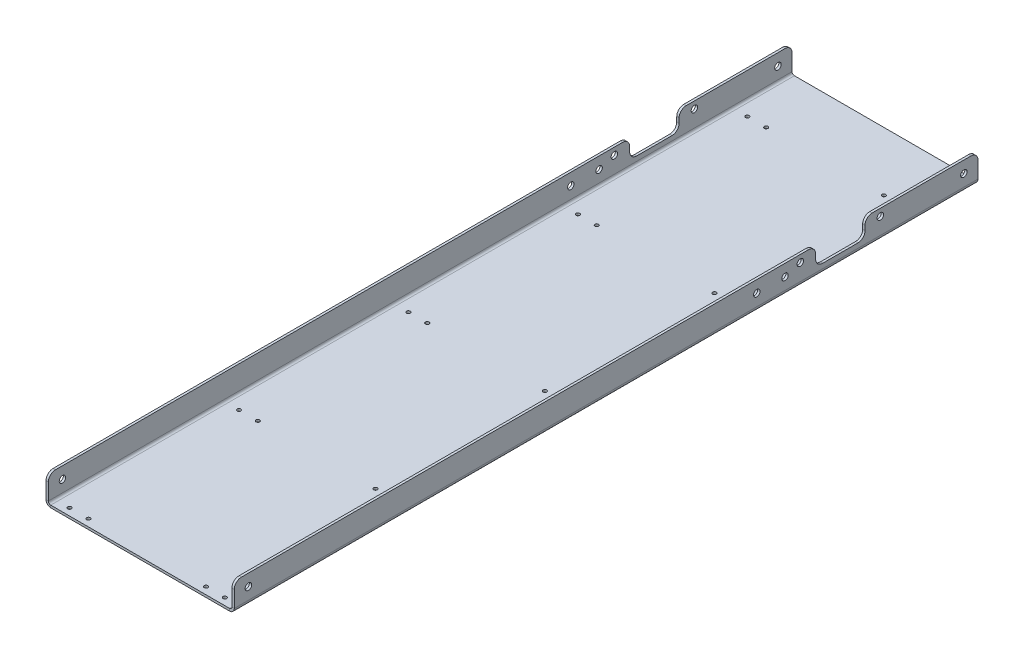
SolidWorks part; units mm, degrees
note: The reader was unsure of these and kept them because the rebuilt part matched: thickness of "Base-Flange1", "Edge-Flange1", "Sheet-Metal1", "Sheet-Metal2", "Sheet-Metal5", "Sheet-Metal6", "Sheet-Metal9"; flange length of "Edge-Flange1".
material "5052-H32"
ref_plane "Front Plane" through (0, 0, 0) normal (0, 0, 1) x (1, 0, 0)
ref_plane "Top Plane" through (0, 0, 0) normal (0, 1, 0) x (1, 0, 0)
ref_plane "Right Plane" through (0, 0, 0) normal (1, 0, 0) x (0, 0, -1)
sketch "Sketch1" plane through (0, 0, 0) normal (0, 1, 0) x (1, 0, 0)
  line L1 (-127, 0) -> (127, 0)
  line L2 (-127, 0) -> (-127, -1003.3)
  line L3 (-127, -1003.3) -> (127, -1003.3)
  line L4 (127, 0) -> (127, -1003.3)
  point P4 (0, 0)
  dimension "D1" = 254
  dimension "D2" = 1003.3
base flange "Base-Flange1" sketch "Sketch1" thickness 3.175 reverse thickness direction no parameters "D1"=3.175
edge flange "Edge-Flange1" sketch "Sketch10" flange profiles "Sketch10", "Sketch11" flange angle 90 flange length 38.1 flange position material inside bend radius 3.175 thickness 3.175 relief rectangular parameters "D1"=3.9688, "D6"=10, "D8"=1
sketch "Sketch10" plane through (-127, 0, 0) normal (-1, 0, 0) x (0, 0, 1)
  line L2 (0, 0) -> (0, 34.925)
  line L3 (0, 34.925) -> (1003.3, 34.925)
  line L4 (1003.3, 34.925) -> (1003.3, 0)
  line L7 (0, 0) -> (1003.3, 0) construction
  line L8 (0, 0) -> (1003.3, 0)
sketch "Sketch11" plane through (127, 0, 0) normal (1, 0, 0) x (0, 0, -1)
  line L0 (-1003.3, 0) -> (0, 0) construction
  line L1 (-1003.3, 0) -> (0, 0)
  line L2 (-1003.3, 0) -> (-1003.3, 34.925)
  line L3 (-1003.3, 34.925) -> (0, 34.925)
  line L4 (0, 34.925) -> (0, 0)
bend "EdgeBend1" bend radius 3.175 bend angle 90 parameters "D5"=1
bend "EdgeBend2" bend radius 3.175 bend angle 90 parameters "D5"=2
sketch "Sketch30" plane through (-127, 0, 0) normal (-1, 0, 0) x (0, 0, 1)
  line L0 (1003.3, 34.925) -> (0, 34.925) construction
  line L1 (152.4, 34.925) -> (219.075, 34.925)
  line L2 (152.4, 34.925) -> (152.4, 9.525)
  line L3 (152.4, 9.525) -> (219.075, 9.525)
  line L4 (219.075, 34.925) -> (219.075, 9.525)
  line L5 (0, 34.925) -> (0, 3.175) construction
  line L6 (1003.3, 0) -> (0, 0) construction
  point P8 (152.4, 22.225)
  point P11 (185.7375, 9.525)
  dimension "D1" = 152.4
  dimension "D2" = 66.675
  dimension "D3" = 9.525
extrude "Cut-Extrude4" cut sketch "Sketch30" against normal through all normal cut yes
sketch "Sketch15" plane through (-127, 0, 0) normal (-1, 0, 0) x (0, 0, 1)
  line L0 (279.4, 34.925) -> (279.4, -3.175) construction
  line L1 (1003.3, 34.925) -> (219.075, 34.925) construction
  line L2 (1003.3, -3.175) -> (0, -3.175) construction
  line L3 (0, 34.925) -> (0, 3.175) construction
  line L4 (0, 19.05) -> (1003.3, 19.05) construction
  line L5 (1003.3, 3.175) -> (1003.3, 34.925) construction
  line L6 (131.7625, 25.4) -> (239.7125, 25.4) construction
  point P12 (260.35, 19.05)
  point P13 (19.05, 19.05)
  point P14 (298.45, 19.05)
  point P15 (984.25, 19.05)
  point P16 (603.25, 19.05)
  dimension "D1" = 279.4
  dimension "D2" = 22.225
  dimension "D3" = 6.35
  dimension "D4" = 19.05
  dimension "D5" = 19.05
  dimension "D6" = 112.7125
  dimension "D7" = 19.05
  dimension "D8" = 19.05
  dimension "D9" = 381
  dimension "D10" = 107.95
hole_wizard "Hole for 1/4 Self-clinching Nuts (S,SS,CLS,CLSS)1" positions "Sketch16" profile "Sketch17" hole size "1/4-20" standard "PEM® Inch" end condition through all
sketch "Sketch16" plane through (-127, 0, 0) normal (-1, 0, 0) x (0, 0, 1)
  point P0 (19.05, 19.05)
  point P6 (260.35, 19.05)
  point P9 (298.45, 19.05)
  point P15 (984.25, 19.05)
  point P18 (239.7125, 25.4)
  point P20 (131.7625, 25.4)
sketch "Sketch17" plane through (-127, 19.05, 19.05) normal (0, 1, 0) x (0, 0, 1)
  line L0 (0, 0) -> (0, 254)
  line L1 (0, 254) -> (4.3688, 254)
  line L2 (4.3688, 254) -> (4.3688, 0)
  line L5 (4.3688, 0) -> (0, 0)
  line L11 (0, -6.35) -> (0, 107.95) construction
  dimension "Thru Hole Dia." = 8.7376
  dimension "Thru Hole Depth" = 254
sketch "Sketch19" plane through (0, 0, 0) normal (0, 1, 0) x (1, 0, 0)
  line L0 (120.65, 0) -> (-120.65, 0) construction
  line L1 (-104.775, 0) -> (104.775, 0) construction
  line L2 (-104.775, 0) -> (-104.775, -1003.3) construction
  line L3 (-104.775, -1003.3) -> (104.775, -1003.3) construction
  line L4 (104.775, 0) -> (104.775, -1003.3) construction
  line L5 (-120.65, -1003.3) -> (120.65, -1003.3) construction
  line L8 (-104.775, -536.575) -> (104.775, -536.575) construction
  line L9 (-79.375, 0) -> (-79.375, -1003.3) construction
  line L10 (-104.775, -765.175) -> (104.775, -765.175) construction
  line L13 (79.375, 0) -> (79.375, -1003.3) construction
  line L16 (-104.775, -993.775) -> (104.775, -993.775) construction
  line L17 (-104.775, -79.375) -> (104.775, -79.375) construction
  line L19 (-104.775, -307.975) -> (104.775, -307.975) construction
  point P8 (0, -993.775)
  point P30 (-79.375, -536.575)
  point P31 (-79.375, -765.175)
  point P32 (79.375, -765.175)
  point P33 (-79.375, -993.775)
  point P34 (79.375, -993.775)
  point P35 (-79.375, -79.375)
  point P36 (79.375, -79.375)
  point P37 (79.375, -536.575)
  point P38 (79.375, -307.975)
  point P39 (-79.375, -307.975)
  dimension "D2" = 104.775
  dimension "D3" = 9.525
  dimension "D4" = 25.4
  dimension "D5" = 228.6
  dimension "D6" = 79.375
  dimension "D11" = 228.6
  dimension "D12" = 228.6
  dimension "D13" = 79.375
hole_wizard "#10 (0.1935) Diameter Hole1" positions "Sketch20" profile "Sketch21" hole size "#10" standard "ANSI Inch" end condition through all
sketch "Sketch20" plane through (0, 0, 0) normal (0, 1, 0) x (1, 0, 0)
  point P87 (104.775, -79.375)
  point P89 (79.375, -79.375)
  point P91 (-79.375, -79.375)
  point P93 (-104.775, -79.375)
  point P95 (-104.775, -307.975)
  point P97 (-79.375, -307.975)
  point P99 (79.375, -307.975)
  point P101 (104.775, -307.975)
  point P103 (104.775, -536.575)
  point P105 (79.375, -536.575)
  point P107 (-79.375, -765.175)
  point P109 (-79.375, -536.575)
  point P111 (-104.775, -536.575)
  point P113 (-104.775, -765.175)
  point P115 (79.375, -765.175)
  point P117 (104.775, -765.175)
  point P119 (104.775, -993.775)
  point P121 (79.375, -993.775)
  point P123 (-79.375, -993.775)
  point P125 (-104.775, -993.775)
sketch "Sketch21" plane through (104.775, 0, 79.375) normal (1, 0, 0) x (0, 0, 1)
  line L0 (0, 0) -> (0, 3.175)
  line L1 (0, 3.175) -> (2.4574, 3.175)
  line L2 (2.4574, 3.175) -> (2.4574, 0)
  line L5 (2.4574, 0) -> (0, 0)
  line L11 (0, -6.35) -> (0, 107.95) construction
  dimension "Thru Hole Dia." = 4.9149
  dimension "Thru Hole Depth" = 3.175
sketch "Sketch25" plane through (0, 0, 0) normal (0, 1, 0) x (1, 0, 0)
  line L0 (-111.125, -174.625) -> (-92.075, -174.625)
  line L1 (-104.775, -152.4) -> (-98.425, -152.4)
  line L2 (-104.775, -152.4) -> (-104.775, -174.625)
  line L3 (-104.775, -174.625) -> (-98.425, -174.625)
  line L4 (-98.425, -152.4) -> (-98.425, -174.625)
  line L5 (-92.075, -174.625) -> (-101.6, -184.15)
  line L6 (-101.6, -184.15) -> (-111.125, -174.625)
  line L7 (-101.6, -184.15) -> (-101.6, -152.4) construction
  line L11 (0, 0) -> (0, -1003.3) construction
  line L12 (-120.65, -1003.3) -> (120.65, -1003.3) construction
  line L13 (-101.6, -184.15) -> (-92.075, -174.625)
  line L14 (-111.125, -174.625) -> (-101.6, -184.15)
  line L15 (-104.775, -152.4) -> (-104.775, -174.625)
  line L16 (-98.425, -152.4) -> (-98.425, -174.625)
  line L17 (101.6, -184.15) -> (101.6, -152.4) construction
  line L18 (101.6, -184.15) -> (111.125, -174.625)
  line L19 (101.6, -184.15) -> (92.075, -174.625)
  line L20 (92.075, -174.625) -> (101.6, -184.15)
  line L21 (111.125, -174.625) -> (92.075, -174.625)
  line L22 (98.425, -152.4) -> (98.425, -174.625)
  line L23 (104.775, -152.4) -> (98.425, -152.4)
  line L24 (104.775, -152.4) -> (104.775, -174.625)
  line L25 (-123.825, 0) -> (-123.825, -1003.3) construction
  line L26 (120.65, 0) -> (-120.65, 0) construction
  point P8 (-101.6, -174.625)
  dimension "D1" = 31.75
  dimension "D2" = 9.525
  dimension "D3" = 6.35
  dimension "D4" = 6.35
  dimension "D5" = 12.7
  dimension "D6" = 152.4
fillet "Fillet5" radius 9.525 12 edges at (-125.4125, 34.925, 1003.3) (125.4125, 34.925, 1003.3) (125.4125, 9.525, 219.075) (125.4125, 34.925, 219.075) (-125.4125, 34.925, 219.075) (-125.4125, 9.525, 219.075) (-125.4125, 9.525, 152.4) (125.4125, 9.525, 152.4) (125.4125, 34.925, 152.4) (-125.4125, 34.925, 152.4) (-125.4125, 34.925, 0) (125.4125, 34.925, 0)
sketch "Bend-Lines1" [suppressed] plane through (0, 0, 0) normal (0, 1, 0) x (1, 0, 0)
sketch "Bounding-Box1" [suppressed] plane through (0, 0, 0) normal (0, 1, 0) x (1, 0, 0)
sheet metal parameters "Sheet-Metal1" thickness 3.175 parameters "D1"=2.9766, "D7"=1.9844
flat pattern "Flat-Pattern1" [suppressed]
sketch "Bend-Lines2" plane through (0, 0, 0) normal (0, 1, 0) x (1, 0, 0)
sketch3d "Bounding-Box2" [suppressed]
  line L0 (127, 0, 0) -> (127, -1003.3, 0) construction
  line L1 (-127, 0, 0) -> (-127, -1003.3, 0) construction
  line L2 (127, 0, 0) -> (-127, 0, 0) construction
  line L3 (127, -1003.3, 0) -> (-127, -1003.3, 0) construction
sheet metal parameters "Sheet-Metal2" thickness 3.175 parameters "D1"=2.9766, "D7"=1.9844
flat pattern "Flat-Pattern1" [suppressed]
sketch "Bend-Lines2" plane through (0, 0, 0) normal (0, 1, 0) x (1, 0, 0)
  line L0 (124.2201, -1003.3) -> (124.2201, 0) construction
  line L1 (-124.2201, 0) -> (-124.2201, -1003.3) construction
  line L2 (124.2201, -1003.3) -> (124.2201, 0) construction
  line L3 (-124.2201, 0) -> (-124.2201, -1003.3) construction
sketch3d "Bounding-Box2" [suppressed]
  line L0 (-159.5402, 0, 0) -> (-159.5402, -1003.3, 0) construction
  line L1 (159.5402, 0, 0) -> (159.5402, -1003.3, 0) construction
  line L2 (-159.5402, 0, 0) -> (159.5402, 0, 0) construction
  line L3 (-159.5402, -1003.3, 0) -> (159.5402, -1003.3, 0) construction
bend of the flat pattern "Flatten-<EdgeBend1>1"
bend of the flat pattern "Flatten-<EdgeBend2>1"
sketch "Sketch15-4" plane through (-124.6152, -3.175, 0) normal (0, -1, 0) x (0, 0, 1)
  line L0 (279.4, 34.925) -> (279.4, -3.175) construction
  line L2 (1003.3, -3.175) -> (0, -3.175) construction
  line L3 (0, 34.925) -> (0, -284.1555) construction
  line L4 (0, 19.05) -> (1003.3, 19.05) construction
  line L5 (1003.3, -284.1555) -> (1003.3, 34.925) construction
  line L6 (252.4125, 34.925) -> (252.4125, 3.9688) construction
  line L7 (119.0625, 34.925) -> (119.0625, 3.9688) construction
  line L9 (119.0625, 3.9688) -> (119.0625, 34.925) construction
  point P12 (260.35, 19.05)
  point P13 (19.05, 19.05)
  point P14 (298.45, 19.05)
  point P15 (984.25, 19.05)
  point P16 (603.25, 19.05)
  point P19 (106.3625, 19.05)
  point P22 (111.125, 19.05)
  dimension "D1" = 279.4
  dimension "D2" = 22.225
  dimension "D3" = 26.9875
  dimension "D4" = 19.05
  dimension "D5" = 19.05
  dimension "D6" = 12.7
  dimension "D7" = 19.05
  dimension "D8" = 19.05
  dimension "D9" = 381
  dimension "D10" = 87.3125
  dimension "D11" = 7.9375
  dimension "D12" = 92.075
sheet metal parameters "Sheet-Metal5" thickness 3.175 parameters "D1"=2.9766, "D7"=1.9844
flat pattern "Flat-Pattern1" [suppressed]
sketch "Bend-Lines2" plane through (0, 0, 0) normal (0, 1, 0) x (1, 0, 0)
  line L0 (124.2201, -1003.3) -> (124.2201, 0) construction
  line L1 (-124.2201, 0) -> (-124.2201, -1003.3) construction
  line L2 (124.2201, -1003.3) -> (124.2201, 0) construction
  line L3 (-124.2201, 0) -> (-124.2201, -1003.3) construction
sketch3d "Bounding-Box2" [suppressed]
  line L0 (-159.5402, 0, 0) -> (-159.5402, -1003.3, 0) construction
  line L1 (159.5402, 0, 0) -> (159.5402, -1003.3, 0) construction
  line L2 (-159.5402, 0, 0) -> (159.5402, 0, 0) construction
  line L3 (-159.5402, -1003.3, 0) -> (159.5402, -1003.3, 0) construction
bend of the flat pattern "Flatten-<EdgeBend1>1"
bend of the flat pattern "Flatten-<EdgeBend2>1"
sketch "Sketch15-1" plane through (-124.6152, -3.175, 0) normal (0, -1, 0) x (0, 0, 1)
  line L0 (279.4, 34.925) -> (279.4, -3.175) construction
  line L2 (1003.3, -3.175) -> (0, -3.175) construction
  line L3 (0, 34.925) -> (0, -284.1555) construction
  line L4 (0, 19.05) -> (1003.3, 19.05) construction
  line L5 (1003.3, -284.1555) -> (1003.3, 34.925) construction
  point P12 (260.35, 19.05)
  point P13 (19.05, 19.05)
  point P14 (298.45, 19.05)
  point P15 (984.25, 19.05)
  point P16 (603.25, 19.05)
  dimension "D1" = 279.4
  dimension "D2" = 22.225
  dimension "D4" = 19.05
  dimension "D5" = 19.05
  dimension "D7" = 19.05
  dimension "D8" = 19.05
  dimension "D9" = 381
sheet metal parameters "Sheet-Metal6" thickness 3.175 parameters "D1"=2.9766, "D7"=1.9844
flat pattern "Flat-Pattern1" [suppressed]
sketch "Bend-Lines2" plane through (0, 0, 0) normal (0, 1, 0) x (1, 0, 0)
  line L0 (124.3905, -1003.3) -> (124.3905, 0) construction
  line L1 (-124.3905, 0) -> (-124.3905, -1003.3) construction
  line L2 (124.3905, -1003.3) -> (124.3905, 0) construction
  line L3 (-124.3905, 0) -> (-124.3905, -1003.3) construction
sketch3d "Bounding-Box2" [suppressed]
  line L0 (159.8809, 0, 0) -> (159.8809, -1003.3, 0) construction
  line L1 (-159.8809, 0, 0) -> (-159.8809, -1003.3, 0) construction
  line L2 (159.8809, 0, 0) -> (-159.8809, 0, 0) construction
  line L3 (159.8809, -1003.3, 0) -> (-159.8809, -1003.3, 0) construction
bend of the flat pattern "Flatten-<EdgeBend1>1"
bend of the flat pattern "Flatten-<EdgeBend2>1"
sketch "Sketch15-1" [suppressed] plane through (-124.9559, -3.175, 0) normal (0, -1, 0) x (0, 0, 1)
  line L0 (279.4, 34.925) -> (279.4, -3.175) construction
  line L2 (1003.3, -3.175) -> (0, -3.175) construction
  line L3 (0, 25.4) -> (0, -275.3118) construction
  line L4 (0, 19.05) -> (1003.3, 19.05) construction
  line L5 (1003.3, -275.3118) -> (1003.3, 25.4) construction
  line L6 (131.7625, 25.4) -> (239.7125, 25.4) construction
  point P12 (260.35, 19.05)
  point P13 (19.05, 19.05)
  point P14 (298.45, 19.05)
  point P15 (984.25, 19.05)
  point P16 (603.25, 19.05)
  dimension "D1" = 279.4
  dimension "D2" = 22.225
  dimension "D3" = 6.35
  dimension "D4" = 19.05
  dimension "D5" = 19.05
  dimension "D6" = 112.7125
  dimension "D7" = 19.05
  dimension "D8" = 19.05
  dimension "D9" = 381
  dimension "D10" = 107.95
sheet metal parameters "Sheet-Metal9" thickness 3.175 parameters "D1"=2.9766, "D7"=1.9844
flat pattern "Flat-Pattern1" [suppressed]
sketch "Bend-Lines2" plane through (0, 0, 0) normal (0, 1, 0) x (1, 0, 0)
  line L0 (124.2201, -1003.3) -> (124.2201, 0) construction
  line L1 (-124.2201, 0) -> (-124.2201, -1003.3) construction
  line L2 (124.2201, -1003.3) -> (124.2201, 0) construction
  line L3 (-124.2201, 0) -> (-124.2201, -1003.3) construction
sketch3d "Bounding-Box2" [suppressed]
  line L0 (-159.5402, 0, 0) -> (-159.5402, -1003.3, 0) construction
  line L1 (159.5402, 0, 0) -> (159.5402, -1003.3, 0) construction
  line L2 (-159.5402, 0, 0) -> (159.5402, 0, 0) construction
  line L3 (-159.5402, -1003.3, 0) -> (159.5402, -1003.3, 0) construction
bend of the flat pattern "Flatten-<EdgeBend1>1"
bend of the flat pattern "Flatten-<EdgeBend2>1"
sketch "Sketch15-4" plane through (-124.6152, -3.175, 0) normal (0, -1, 0) x (0, 0, 1)
  line L0 (279.4, 34.925) -> (279.4, -3.175) construction
  line L2 (1003.3, -3.175) -> (0, -3.175) construction
  line L3 (0, 34.925) -> (0, -284.1555) construction
  line L4 (0, 19.05) -> (1003.3, 19.05) construction
  line L5 (1003.3, -284.1555) -> (1003.3, 34.925) construction
  line L6 (252.4125, 34.925) -> (252.4125, 3.9688) construction
  line L7 (119.0625, 34.925) -> (119.0625, 3.9688) construction
  line L9 (119.0625, 3.9688) -> (119.0625, 34.925) construction
  point P12 (260.35, 19.05)
  point P13 (19.05, 19.05)
  point P14 (298.45, 19.05)
  point P15 (984.25, 19.05)
  point P16 (603.25, 19.05)
  point P19 (106.3625, 19.05)
  point P22 (111.125, 19.05)
  dimension "D1" = 279.4
  dimension "D2" = 22.225
  dimension "D3" = 26.9875
  dimension "D4" = 19.05
  dimension "D5" = 19.05
  dimension "D6" = 12.7
  dimension "D7" = 19.05
  dimension "D8" = 19.05
  dimension "D9" = 381
  dimension "D10" = 87.3125
  dimension "D11" = 7.9375
  dimension "D12" = 92.075
